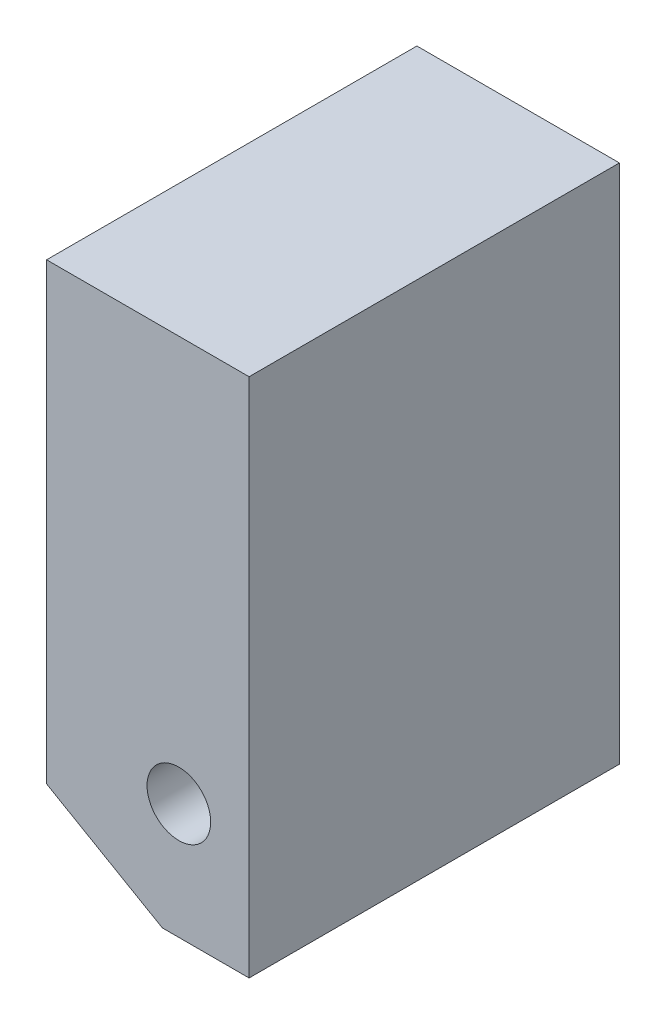
SolidWorks part; units mm, degrees
ref_plane "Front Plane" through (0, 0, 0) normal (0, 0, 1) x (1, 0, 0)
ref_plane "Top Plane" through (0, 0, 0) normal (0, 1, 0) x (1, 0, 0)
ref_plane "Right Plane" through (0, 0, 0) normal (1, 0, 0) x (0, 0, -1)
sketch "Sketch1" plane through (0, 0, 0) normal (0, 0, 1) x (1, 0, 0)
  line L0 (-8.1502, -18.2688) -> (1.8498, -24.0423)
  line L1 (1.8498, -24.0423) -> (9.3498, -24.0423)
  line L2 (-8.1502, -18.2688) -> (-8.1502, 20.9577)
  line L3 (-8.1502, 20.9577) -> (9.3498, 20.9577)
  line L4 (9.3498, -24.0423) -> (9.3498, 20.9577)
  line L5 (-8.1502, -18.2688) -> (9.3498, 20.9577) construction
  line L6 (-8.1502, 20.9577) -> (9.3498, -24.0423) construction
  point P0 (0, 0)
  point P2 (1.3818, -22.4086)
  point P8 (0, 0)
  point P9 (0, 0)
  dimension "D1" = 17.5
  dimension "D2" = 45
  dimension "D3" = 30
  dimension "D4" = 7.5
extrude "Boss-Extrude1" add sketch "Sketch1" along normal blind 32
sketch "Sketch2" plane through (0, 0, 0) normal (0, 0, -1) x (-1, 0, 0)
  line L0 (-1.8498, -24.0423) -> (-9.3498, -24.0423) construction
  line L1 (8.1502, 20.9577) -> (8.1502, -18.2688) construction
  circle A0 centre (-3.2798, -14.0423) radius 2.75
  circle A1 centre (-3.2798, -20.3923) radius 2
  point P4 (0, 0)
  dimension "D1" = 5.5
  dimension "D2" = 4
  dimension "D3" = 6.35
  dimension "D4" = 10
  dimension "D6" = 11.43
extrude "Cut-Extrude1" cut sketch "Sketch2" against normal through all contours A0 region at (3.2798, -14.0423, 0)
extrude "Cut-Extrude2" cut sketch "Sketch2<3>" against normal blind 11 contours A1 region at (3.2798, -20.3923, 0)
sketch "Sketch2<3>" plane through (0, 0, 0) normal (0, 0, -1) x (-1, 0, 0) same geometry as "Sketch2"
hole_wizard "M2.5x0.45 Tapped Hole1" positions "Sketch3" profile "Sketch5" tap size "M2.5x0.45" standard "ANSI Metric"
sketch "Sketch3" plane through (0, -24.0423, 0) normal (0, -1, 0) x (-1, 0, 0)
  line L2 (-1.8498, 0) -> (-9.3498, 0) construction
  point P0 (-5.5998, -16)
  point P6 (0, 0)
  point P7 (0, 0)
  point P11 (0, 0)
  point P14 (-5.5998, 0)
  dimension "D1" = 0
  dimension "D2" = 16
sketch "Sketch5" plane through (5.5998, -24.0423, 16) normal (1, 0, 0) x (0, 0, -1)
  line L0 (0, 0) -> (0, 8.1159)
  line L1 (0, 8.1159) -> (1.025, 7.5)
  line L2 (1.025, 7.5) -> (1.025, 0.25)
  line L3 (1.025, 0.25) -> (1.275, 0)
  line L5 (1.275, 0) -> (0, 0)
  line L6 (-1.025, 0.25) -> (-1.275, 0) construction
  line L10 (0, 8.1159) -> (-1.025, 7.5) construction
  line L11 (0, -6.35) -> (0, 107.95) construction
  dimension "Tap Drill Dia." = 2.05
  dimension "Tap Drill Depth" = 7.5
  dimension "Near C'Sink Dia." = 2.55
  dimension "Near C'Sink Angle" = 90
  dimension "Drill Angle" = 118
cosmetic thread "Hole Thread1" parameters "D1"=5, "D2"=2.5
